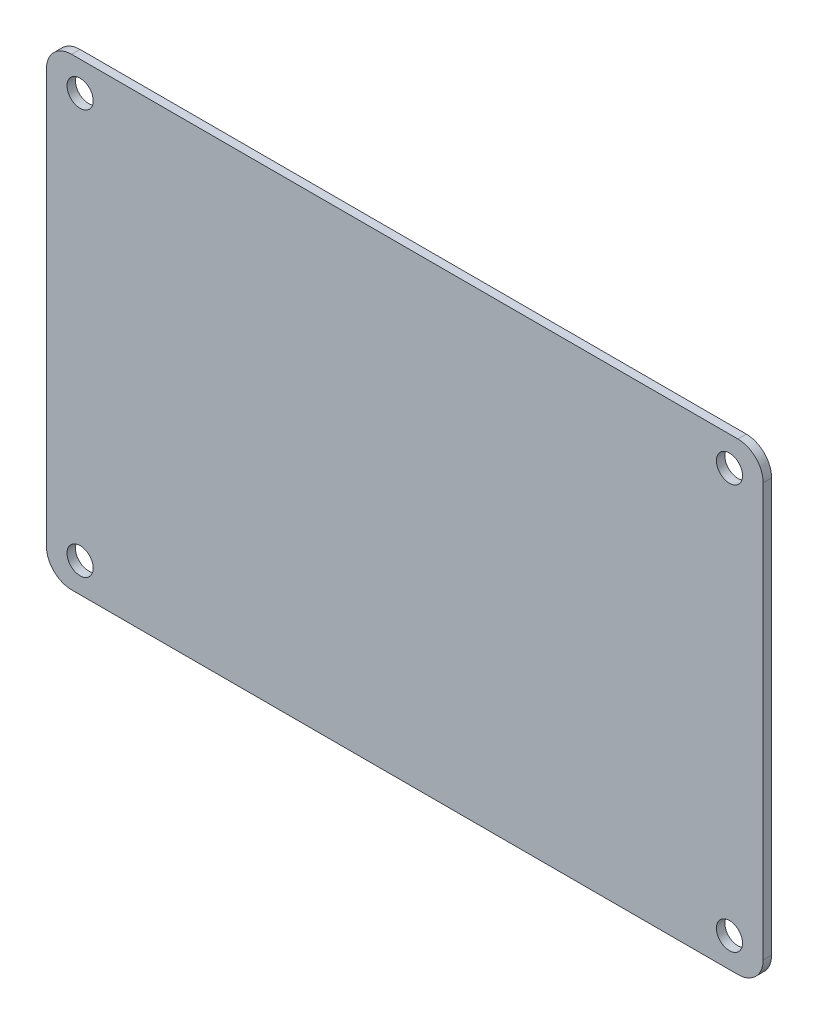
SolidWorks part; units mm, degrees
ref_plane "Front Plane" through (0, 0, 0) normal (0, 0, 1) x (1, 0, 0)
ref_plane "Top Plane" through (0, 0, 0) normal (0, 1, 0) x (1, 0, 0)
ref_plane "Right Plane" through (0, 0, 0) normal (1, 0, 0) x (0, 0, -1)
sketch "Sketch1" plane through (0, 0, 0) normal (0, 0, 1) x (1, 0, 0)
  line L0 (-38.5, 0) -> (0, 0) construction
  line L1 (-39.5, 27.5) -> (39.5, 27.5)
  line L2 (-42.5, 24.5) -> (-42.5, -24.5)
  line L3 (-39.5, -27.5) -> (39.5, -27.5)
  line L4 (42.5, 24.5) -> (42.5, -24.5)
  line L5 (-42.5, 27.5) -> (42.5, -27.5) construction
  line L6 (-42.5, -27.5) -> (42.5, 27.5) construction
  line L7 (-38.5, 0) -> (-38.5, -24) construction
  arc A3 (-39.5, 27.5) -> (-42.5, 24.5) centre (-39.5, 24.5) ccw
  arc A4 (-39.5, -27.5) -> (-42.5, -24.5) centre (-39.5, -24.5) cw
  arc A5 (42.5, -24.5) -> (39.5, -27.5) centre (39.5, -24.5) cw
  arc A6 (39.5, 27.5) -> (42.5, 24.5) centre (39.5, 24.5) cw
  circle A7 centre (-38.5, -24) radius 1.55
  point P0 (0, 0)
  dimension "D3" = 38.5
  dimension "D4" = 3.1
  dimension "D5" = 3
  dimension "D6" = 3
  dimension "D7" = 3
  dimension "D8" = 3
  dimension "D1" = 85
  dimension "D2" = 55
  dimension "D9" = 24
extrude "Boss-Extrude1" add sketch "Sketch1" along normal blind 1
sketch "Sketch3" plane through (0, 0, 0) normal (0, 0, 1) x (1, 0, 0)
  line L0 (0, 0) -> (38.5, 0) construction
  line L1 (38.5, 0) -> (38.5, -24) construction
  circle A1 centre (38.5, -24) radius 1.55
  dimension "D1" = 3.1
  dimension "D2" = 38.5
extrude "Cut-Extrude7" cut sketch "Sketch3" along normal up to next
sketch "Sketch4" plane through (0, 0, 1) normal (0, 0, 1) x (1, 0, 0)
  line L0 (0, 0) -> (-38.5, 0) construction
  line L1 (-38.5, 0) -> (-38.4978, 0.0203)
  line L2 (-38.5, 0) -> (-38.5, 24) construction
  circle A0 centre (-38.5, 24) radius 1.55
  dimension "D3" = 3.1
  dimension "D1" = 38.5
  dimension "D2" = 24
extrude "Cut-Extrude8" cut sketch "Sketch4" against normal through all contours A0 region at (-38.5, 24, 1)
sketch "Sketch7" plane through (0, 0, 1) normal (0, 0, 1) x (1, 0, 0)
  line L0 (0, 0) -> (38.5, 0) construction
  line L1 (38.5, 0) -> (38.5, 24) construction
  circle A0 centre (38.5, 24) radius 1.55
  dimension "D3" = 3.1
  dimension "D1" = 38.5
  dimension "D2" = 24
extrude "Cut-Extrude9" cut sketch "Sketch7" against normal through all contours A0 region at (38.5, 24, 1)
